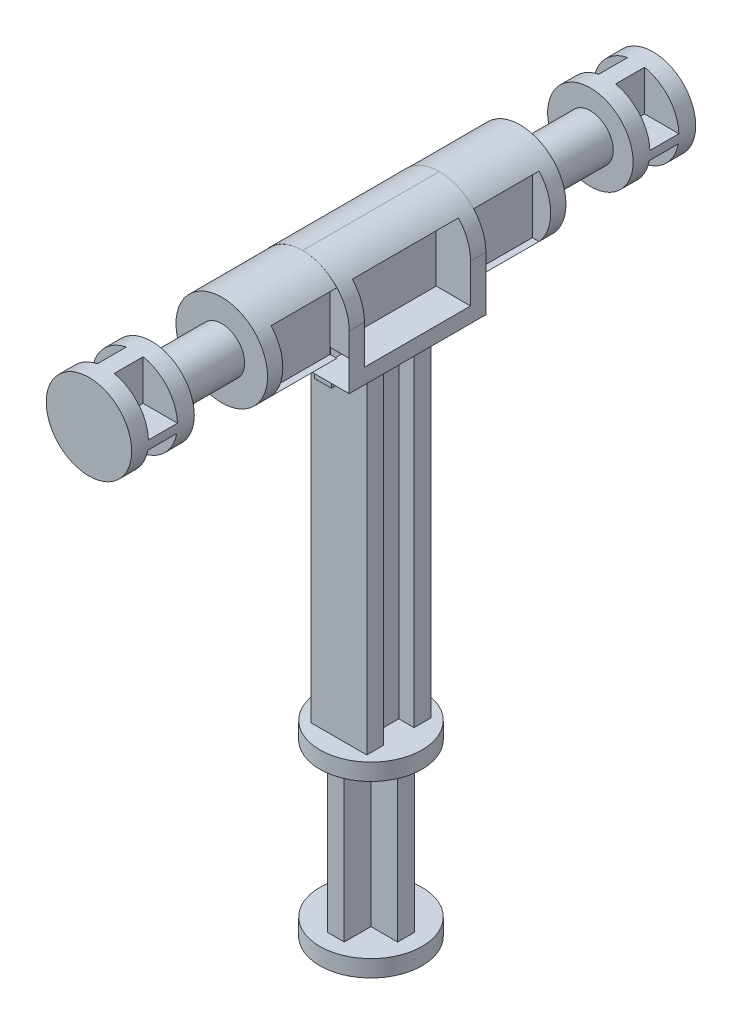
SolidWorks part; units mm, degrees
ref_plane "Front Plane" through (0, 0, 0) normal (0, 0, 1) x (1, 0, 0)
ref_plane "Top Plane" through (0, 0, 0) normal (0, 1, 0) x (1, 0, 0)
ref_plane "Right Plane" through (0, 0, 0) normal (1, 0, 0) x (0, 0, -1)
sketch "Sketch1" plane through (0, 0, 0) normal (0, 1, 0) x (1, 0, 0)
  circle A0 centre (0, 0) radius 3.35
  dimension "D1" = 6.7
extrude "Boss-Extrude1" add sketch "Sketch1" along normal blind 1.1
sketch "Sketch2" plane through (0, 1.1, 0) normal (0, 1, 0) x (1, 0, 0)
  line L0 (0, -1000) -> (0, -2.3) construction
  line L1 (-0.55, -2.3) -> (0.55, -2.3)
  line L2 (-2.3, -0.55) -> (-2.3, 0.55)
  line L3 (-0.55, 2.3) -> (0.55, 2.3)
  line L4 (2.3, -0.55) -> (2.3, 0.55)
  line L9 (-2.3, 0.55) -> (-0.55, 0.55)
  line L10 (-0.55, 2.3) -> (-0.55, 0.55)
  line L13 (2.3, 0.55) -> (0.55, 0.55)
  line L14 (0.55, 2.3) -> (0.55, 0.55)
  line L17 (-2.3, -0.55) -> (-0.55, -0.55)
  line L18 (-0.55, -2.3) -> (-0.55, -0.55)
  line L21 (2.3, -0.55) -> (0.55, -0.55)
  line L22 (0.55, -2.3) -> (0.55, -0.55)
  line L23 (-1000, 0) -> (-2.3, 0) construction
  line L24 (0, 2.3) -> (0, 1003.6451) construction
  point P0 (0, 0)
  dimension "D2" = 1.1
  dimension "D3" = 1.1
  dimension "D4" = 1.1
  dimension "D5" = 1.1
extrude "Boss-Extrude2" add sketch "Sketch2" along normal blind 10.05
sketch "Sketch3" plane through (0, 11.15, 0) normal (0, 1, 0) x (1, 0, 0)
  circle A0 centre (0, 0) radius 3.35
extrude "Boss-Extrude3" add sketch "Sketch3" along normal blind 1.1
sketch "Sketch5" plane through (0, 12.25, 0) normal (0, 1, 0) x (1, 0, 0)
  line L0 (-1.825, 1) -> (-1.825, 2.1)
  line L1 (-1.825, -2.1) -> (1.825, -2.1)
  line L2 (-1.825, -2.1) -> (-1.825, -1)
  line L3 (-1.825, 2.1) -> (1.825, 2.1)
  line L4 (1.825, -2.1) -> (1.825, -1)
  line L5 (1.825, 1) -> (1.825, 2.1)
  line L7 (-1.825, 1) -> (-0.825, 1)
  line L9 (-1.825, -1) -> (-0.825, -1)
  line L10 (-0.825, 1) -> (-0.825, -1)
  line L11 (1.825, -1) -> (0.825, -1)
  line L13 (1.825, 1) -> (0.825, 1)
  line L14 (0.825, -1) -> (0.825, 1)
  point P0 (0, 0)
  dimension "D1" = 3.65
  dimension "D2" = 4.2
  dimension "D3" = 1.1
  dimension "D4" = 1.1
  dimension "D5" = 1.1
  dimension "D6" = 1.1
  dimension "D7" = 1
  dimension "D8" = 1
extrude "Boss-Extrude4" add sketch "Sketch5" along normal blind 22.3
sketch "Sketch6" plane through (0, 34.55, 0) normal (0, 1, 0) x (1, 0, 0)
  line L1 (-3.05, -4.475) -> (3.05, -4.475)
  line L2 (-3.05, -4.475) -> (-3.05, 4.475)
  line L3 (-3.05, 4.475) -> (3.05, 4.475)
  line L4 (3.05, -4.475) -> (3.05, 4.475)
  line L5 (-3.05, -4.475) -> (3.05, 4.475) construction
  line L6 (-3.05, 4.475) -> (3.05, -4.475) construction
  point P0 (0, 0)
  dimension "D1" = 6.1
  dimension "D2" = 8.95
extrude "Boss-Extrude5" add sketch "Sketch6" along normal blind 6.6
sketch "Sketch7" plane through (0, 0, 4.475) normal (0, 0, 1) x (1, 0, 0)
  line L0 (-3.05, 41.15) -> (3.05, 41.15) construction
  circle A0 centre (0, 38.15) radius 3
  dimension "D1" = 6
  dimension "D2" = 3
extrude "Boss-Extrude6" add sketch "Sketch7" along normal blind 5.3
sketch "Sketch8" plane through (0, 0, 9.775) normal (0, 0, 1) x (1, 0, 0)
  circle A0 centre (0, 38.15) radius 1.5
  dimension "D1" = 3
extrude "Boss-Extrude7" add sketch "Sketch8" along normal blind 4.6
sketch "Sketch9" plane through (0, 0, 14.375) normal (0, 0, 1) x (1, 0, 0)
  circle A0 centre (0, 38.15) radius 2.8
  dimension "D1" = 5.6
extrude "Boss-Extrude8" add sketch "Sketch9" along normal blind 4.1
fillet "Fillet2" radius 3.05 2 edges at (3.05, 41.15, 0) (-3.05, 41.15, 0)
ref_plane "Plane2" through (-3.05, 0, 0) normal (-1, 0, 0) x (0, 0, 1)
sketch "Sketch10" plane through (-3.05, 0, 0) normal (-1, 0, 0) x (0, 0, 1)
  line L0 (-4.475, 34.55) -> (4.475, 34.55) construction
  line L1 (-3.475, 35.55) -> (3.475, 35.55)
  line L2 (-3.475, 35.55) -> (-3.475, 40.15)
  line L3 (-3.475, 40.15) -> (3.475, 40.15)
  line L4 (3.475, 35.55) -> (3.475, 40.15)
  line L5 (-3.475, 35.55) -> (3.475, 40.15) construction
  line L6 (-3.475, 40.15) -> (3.475, 35.55) construction
  line L7 (4.475, 38.1) -> (4.475, 34.55) construction
  line L8 (-4.475, 38.1) -> (-4.475, 34.55) construction
  line L9 (-4.475, 41.15) -> (4.475, 41.15) construction
  point P0 (0, 37.85)
  dimension "D1" = 1
  dimension "D2" = 1
  dimension "D3" = 1
  dimension "D4" = 1
extrude "Cut-Extrude1" cut sketch "Sketch10" against normal blind 2.25 and the other way through all
sketch "Sketch11" plane through (-3.05, 0, 0) normal (-1, 0, 0) x (0, 0, 1)
  line L0 (4.475, 35.15) -> (4.475, 41.15) construction
  line L1 (4.475, 36.15) -> (8.775, 36.15)
  line L2 (4.475, 36.15) -> (4.475, 40.15)
  line L3 (4.475, 40.15) -> (8.775, 40.15)
  line L4 (8.775, 36.15) -> (8.775, 40.15)
  line L5 (4.475, 36.15) -> (8.775, 40.15) construction
  line L6 (4.475, 40.15) -> (8.775, 36.15) construction
  line L7 (9.775, 36.65) -> (9.775, 39.65) construction
  line L8 (4.475, 35.15) -> (9.775, 35.15) construction
  line L9 (9.775, 41.15) -> (4.475, 41.15) construction
  point P0 (6.625, 38.15)
  dimension "D1" = 0
  dimension "D2" = 1
  dimension "D3" = 1
  dimension "D4" = 1
extrude "Cut-Extrude2" cut sketch "Sketch11" against normal blind 1.25
sketch "Sketch12" plane through (-3.05, 0, 0) normal (-1, 0, 0) x (0, 0, 1)
  line L0 (18.475, 40.95) -> (14.375, 40.95) construction
  line L1 (15.475, 38.2476) -> (17.375, 38.2476)
  line L2 (15.475, 38.2476) -> (15.475, 40.95)
  line L3 (15.475, 40.95) -> (17.375, 40.95)
  line L4 (17.375, 38.2476) -> (17.375, 40.95)
  line L5 (15.475, 38.2476) -> (17.375, 40.95) construction
  line L6 (15.475, 40.95) -> (17.375, 38.2476) construction
  line L7 (18.475, 35.35) -> (18.475, 40.95) construction
  line L8 (15.475, 35.3779) -> (17.375, 35.3779)
  line L9 (15.475, 35.3779) -> (15.475, 37.644)
  line L10 (15.475, 37.644) -> (17.375, 37.644)
  line L11 (17.375, 35.3779) -> (17.375, 37.644)
  line L12 (15.475, 35.3779) -> (17.375, 37.644) construction
  line L13 (15.475, 37.644) -> (17.375, 35.3779) construction
  line L14 (14.375, 40.95) -> (14.375, 35.35) construction
  point P0 (16.425, 39.5988)
  point P7 (16.425, 36.5109)
  dimension "D1" = 1.1
  dimension "D2" = 1.1
  dimension "D3" = 1.1
  dimension "D4" = 1.1
extrude "Cut-Extrude3" cut sketch "Sketch12" against normal blind 2.5
mirror "Mirror1" about plane through (0, 0, 0) normal (1, 0, 0) of "Cut-Extrude3", "Cut-Extrude2", "Cut-Extrude1"
mirror "Mirror3" about plane through (0, 0, 0) normal (0, 0, 1) of "Mirror1", "Cut-Extrude2", "Cut-Extrude3", "Boss-Extrude8", "Boss-Extrude7", "Boss-Extrude6"
sketch "Sketch13" plane through (0, 0, 0) normal (0, 0, 1) x (1, 0, 0)
  line L0 (-1.825, 34.55) -> (1.825, 34.55) construction
  line L1 (-0.56, 34.55) -> (0.56, 34.55)
  line L2 (-0.56, 34.55) -> (-0.56, 32.95)
  line L3 (-0.56, 32.95) -> (0.56, 32.95)
  line L4 (0.56, 34.55) -> (0.56, 32.95)
  line L5 (0, 0) -> (0, 1.6) construction
  dimension "D1" = 1.6
  dimension "D2" = 1.12
extrude "Boss-Extrude9" add sketch "Sketch13" along normal mid plane 6.3
sketch "Sketch14" plane through (0, 0, 0) normal (0, -1, 0) x (1, 0, 0)
  circle A0 centre (0, 0) radius 1.05
  dimension "D1" = 2.1
extrude "Boss-Extrude10" add sketch "Sketch14" along normal mid plane 1
sketch "Sketch15" plane through (0, -0.5, 0) normal (0, -1, 0) x (1, 0, 0)
  circle A0 centre (0, 0) radius 1.2
  dimension "D1" = 2.4
extrude "Boss-Extrude11" add sketch "Sketch15" along normal mid plane 1
chamfer "Chamfer1" distance 0.3 angle 45 1 edges at (0, -1, -1.2)
